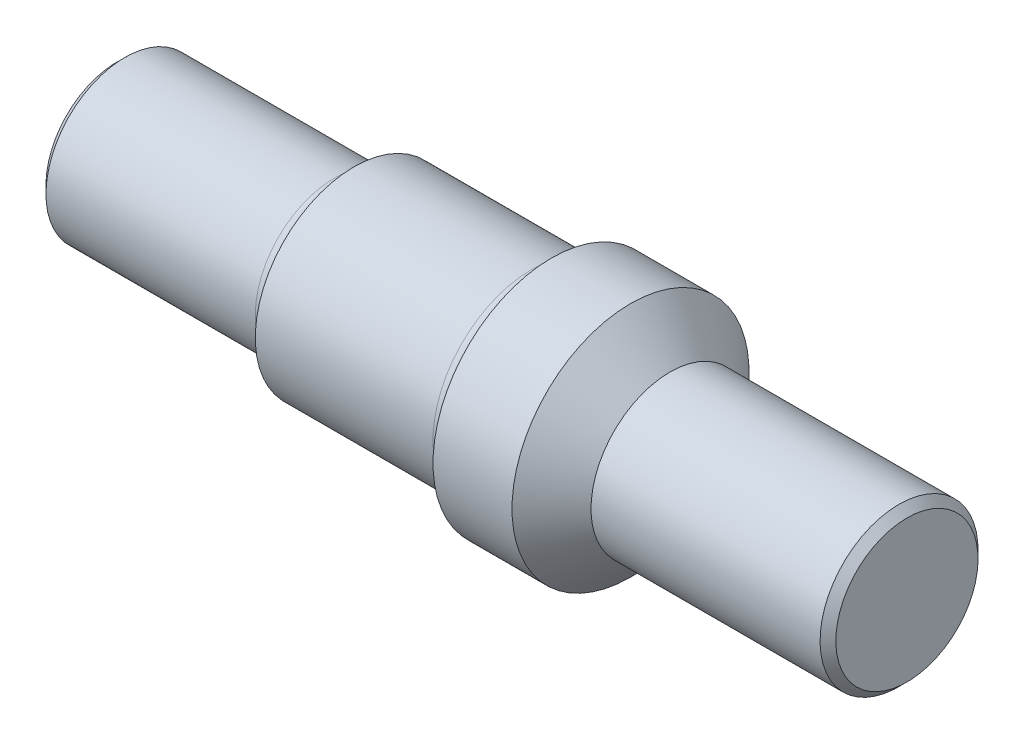
SolidWorks part; units mm, degrees
ref_plane "Front Plane" through (0, 0, 0) normal (0, 0, 1) x (1, 0, 0)
ref_plane "Top Plane" through (0, 0, 0) normal (0, 1, 0) x (1, 0, 0)
ref_plane "Right Plane" through (0, 0, 0) normal (1, 0, 0) x (0, 0, -1)
sketch "Sketch1" plane through (0, 0, 0) normal (0, 0, 1) x (1, 0, 0)
  line L0 (0, 0) -> (0, 10)
  line L1 (0, 10) -> (30, 10)
  line L2 (30, 10) -> (30, 12.5)
  line L3 (30, 12.5) -> (55, 12.5)
  line L4 (55, 12.5) -> (55, 15)
  line L7 (70, 10) -> (100, 10)
  line L8 (100, 10) -> (100, 0)
  line L9 (100, 0) -> (0, 0)
  line L10 (55, 15) -> (65, 15)
  line L11 (65, 15) -> (70, 10)
  point P8 (50, 0)
  point P9 (42.5, 12.5)
  point P12 (85, 10)
  point P15 (15, 10)
  dimension "D1" = 30
  dimension "D2" = 25
  dimension "D3" = 2.5
  dimension "D4" = 30
  dimension "D5" = 10
  dimension "D6" = 10
  dimension "D7" = 45
  dimension "D8" = 2.5
  dimension "D9" = 70
  dimension "D10" = 27.5
  dimension "D11" = 42.5
revolve "Revolve1" add sketch "Sketch1" angle 360 about L9
fillet "Fillet1" radius 2.5 2 edges at (55, 12.5, 0) (30, 10, 0)
chamfer "Chamfer1" distance 1 angle 45 2 edges at (100, 10, 0) (0, 10, 0)
